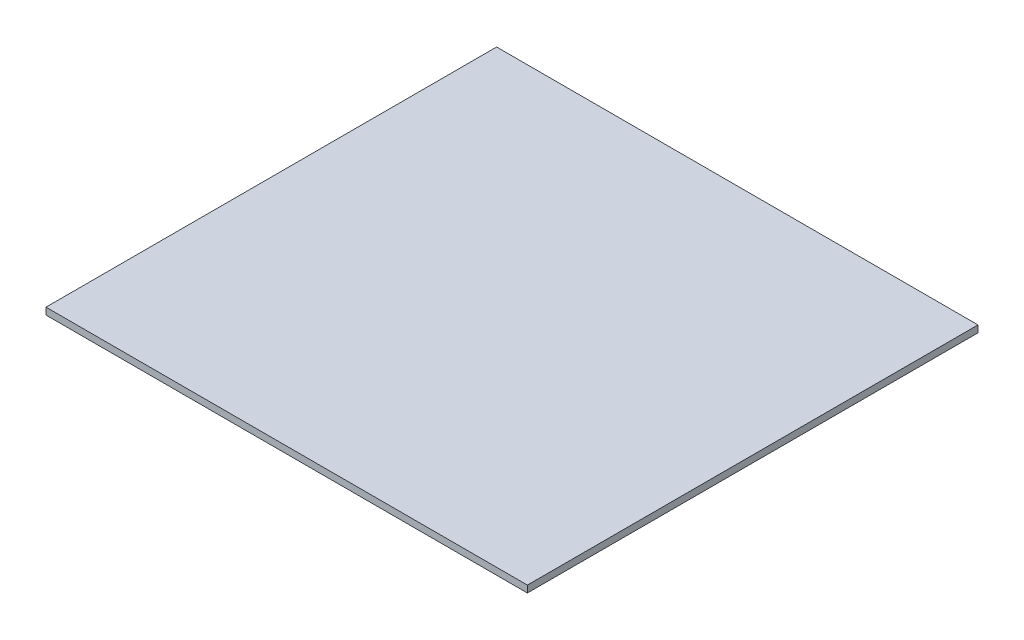
SolidWorks part; units mm, degrees
ref_plane "Front Plane" through (0, 0, 0) normal (0, 0, 1) x (1, 0, 0)
ref_plane "Top Plane" through (0, 0, 0) normal (0, 1, 0) x (1, 0, 0)
ref_plane "Right Plane" through (0, 0, 0) normal (1, 0, 0) x (0, 0, -1)
sketch "Sketch2" plane through (0, 0, 0) normal (0, 0, 1) x (1, 0, 0)
  line L0 (0, 40) -> (-350, 40)
  line L1 (-350, 40) -> (-350, 30)
  line L2 (-350, 30) -> (-225, 30)
  line L3 (-225, 30) -> (-225, 0)
  line L4 (-225, 0) -> (0, 0)
  line L5 (0, 40) -> (0, 0)
  dimension "D1" = 225
  dimension "D2" = 350
  dimension "D3" = 40
  dimension "D4" = 10
extrude "Boss-Extrude1" add sketch "Sketch2" along normal mid plane 555.25
mirror "Mirror1" about plane through (0, 40, 277.625) normal (-1, 0, 0) of "Boss-Extrude1"
sketch "Sketch3" plane through (0, 0, 277.625) normal (0, 0, 1) x (1, 0, 0)
  line L1 (-350, 40) -> (350, 40)
  line L2 (-350, 40) -> (-350, 30)
  line L3 (-350, 30) -> (350, 30)
  line L4 (350, 40) -> (350, 30)
  line L5 (-350, 40) -> (-350, 30) construction
  line L6 (350, 40) -> (350, 30) construction
  line L7 (350, 40) -> (-350, 40) construction
extrude "Boss-Extrude2" add sketch "Sketch3" along normal blind 50
sketch "Sketch4" plane through (0, 0, -277.625) normal (0, 0, -1) x (-1, 0, 0)
  line L0 (-350, 40) -> (-350, 30) construction
  line L1 (-350, 40) -> (350, 40)
  line L2 (-350, 40) -> (-350, 30)
  line L3 (-350, 30) -> (350, 30)
  line L4 (350, 40) -> (350, 30)
  line L5 (-350, 30) -> (-225, 30) construction
  line L6 (350, 40) -> (350, 30) construction
  line L7 (-350, 40) -> (350, 40) construction
extrude "Boss-Extrude3" add sketch "Sketch4" along normal blind 50
